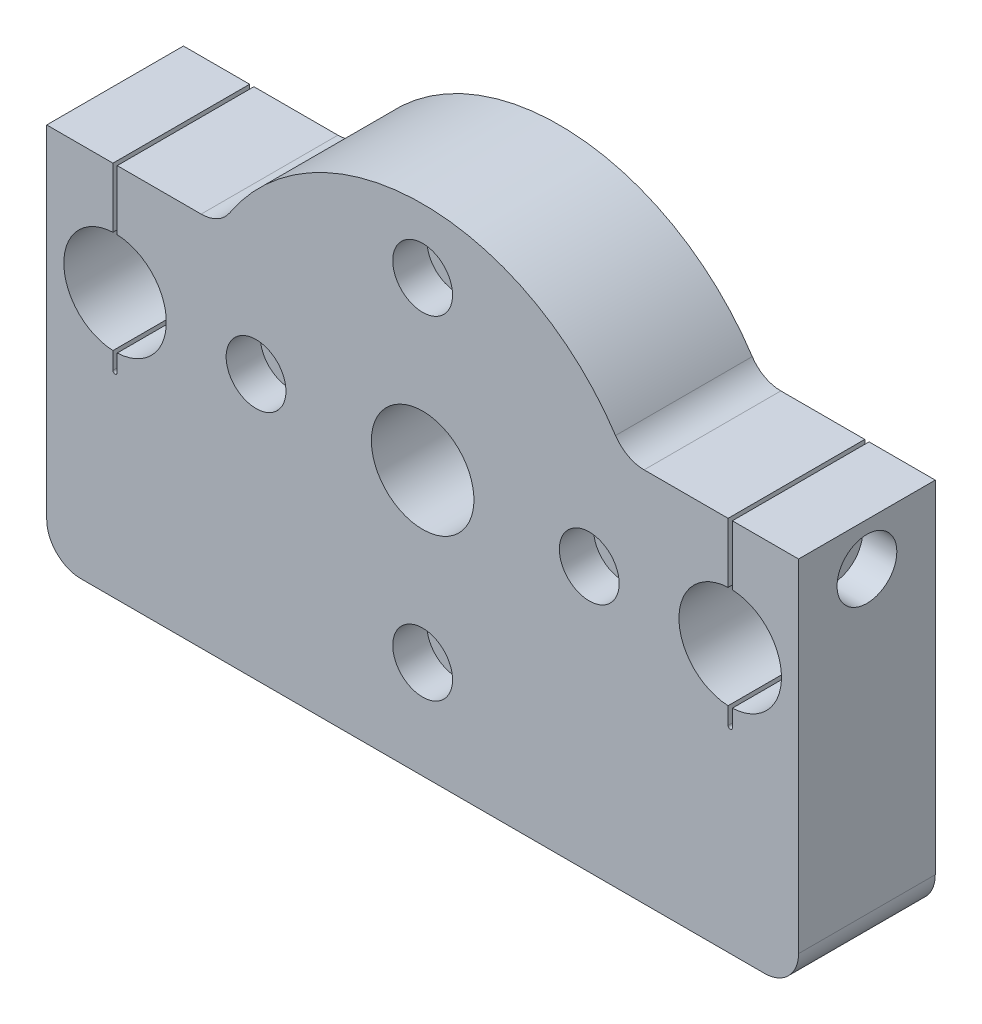
SolidWorks part; units mm, degrees
material "6061 Alloy"
ref_plane "Front" through (0, 0, 0) normal (0, 0, 1) x (1, 0, 0)
ref_plane "Top" through (0, 0, 0) normal (0, 1, 0) x (1, 0, 0)
ref_plane "Right" through (0, 0, 0) normal (1, 0, 0) x (0, 0, -1)
ref_axis "Axis" through (0, 0, -80.9) along (0, 0, 1)
sketch "Bolt circle" plane through (0, 0, 0) normal (0, 0, 1) x (1, 0, 0)
  line L0 (0, 36.5125) -> (0, 25.4) construction
  line L3 (37.5671, 20.6375) -> (69.85, 20.6375)
  line L5 (37.5671, 20.6375) -> (-37.5671, 20.6375) construction
  line L6 (-37.5671, 20.6375) -> (-69.85, 20.6375)
  line L30 (69.85, 20.6375) -> (69.85, -49.2125)
  line L31 (69.85, -49.2125) -> (-69.85, -49.2125)
  line L34 (-69.85, 20.6375) -> (-69.85, -49.2125)
  line L35 (0, 0) -> (0, -49.2125) construction
  circle A0 centre (0, 0) radius 36.5125 construction
  circle A1 centre (0, 0) radius 25.4 construction
  circle A2 centre (0, 0) radius 30.9562 construction
  arc A5 (-37.5671, 20.6375) -> (37.5671, 20.6375) centre (0, 0) cw
  circle A7 centre (0, 0) radius 12.7 construction
  point P0 (0, -36.5125)
  point P7 (0, 30.9562)
  point P34 (0, 42.8625)
  dimension "D1" = 73.025
  dimension "D2" = 50.8
  dimension "D3" = 69.85
  dimension "D12" = 139.7
  dimension "D13" = 25.4
  dimension "D4" = 12.7
  dimension "D16" = 6.35
extrude "Base" add sketch "Bolt circle" along normal mid plane 25.4
hole_wizard "Tube counterbore" positions "Sketch7" profile "Sketch6" counterbore size "1/4" standard "Ansi Inch" end condition through all
sketch "Sketch7" plane through (0, 0, 12.7) normal (0, 0, 1) x (1, 0, 0)
  circle A0 centre (0, 0) radius 30.9562 construction
  point P1 (0, 30.9562)
  dimension "D1" = 61.9125
sketch "Sketch6" plane through (0, 30.9562, 12.7) normal (1, 0, 0) x (0, -1, 0)
  line L0 (0, 0) -> (0, 25.4)
  line L1 (0, 25.4) -> (3.3782, 25.4)
  line L3 (3.3782, 25.4) -> (3.3782, 6.35)
  line L4 (3.3782, 6.35) -> (5.5562, 6.35)
  line L5 (5.5562, 6.35) -> (5.5562, 0)
  line L7 (5.5562, 0) -> (0, 0)
  line L11 (0, -6.35) -> (0, 107.95) construction
  dimension "Thru Hole Dia." = 6.7564
  dimension "Thru Hole Depth" = 25.4
  dimension "C'Bore Dia." = 11.1125
  dimension "C'Bore Depth" = 6.35
cosmetic thread "Hole Thread2" parameters "D2"=16.7564
pattern_circular "Tube counterbore pattern" count 4 over 360 about axis through (0, 0, -80.9) along (0, 0, 1) of "Tube counterbore"
sketch "Sketch8" plane through (0, 0, -12.7) normal (0, 0, -1) x (-1, 0, 0)
  circle A0 centre (0, 0) radius 36.5125
  dimension "D1" = 73.025
extrude "Structure_tube_recess" cut sketch "Sketch8" against normal blind 7.62
sketch "Sketch9" plane through (0, 0, -5.08) normal (0, 0, -1) x (-1, 0, 0)
  circle A0 centre (0, 0) radius 9.525
  dimension "D1" = 19.05
extrude "Lead_screw_thru_hole" cut sketch "Sketch9" against normal through all
sketch "Sketch13" plane through (0, 0, 12.7) normal (0, 0, 1) x (1, 0, 0)
  line L0 (0, 0) -> (0, -62.7576) construction
  circle A0 centre (57.15, 0) radius 9.525
  circle A1 centre (-57.15, 0) radius 9.525
  dimension "D3" = 19.05
  dimension "D1" = 114.3
extrude "Rail_bore_pilot_hole" cut sketch "Sketch13" against normal through all
sketch "Sketch14" plane through (0, 0, -5.08) normal (0, 0, -1) x (-1, 0, 0)
  line L0 (20.6813, 24.0896) -> (19.6028, 22.9247)
  line L1 (24.176, 20.854) -> (23.0974, 19.6891)
  line L2 (21.8894, 21.8894) -> (-21.8894, -21.8894) construction
  line L3 (20.1421, 23.5072) -> (23.6367, 20.2716) construction
  line L4 (50, 0) -> (-50, 0) construction
  circle A0 centre (-21.8894, -21.8894) radius 2.3813
  arc A1 (24.176, 20.854) -> (20.6813, 24.0896) centre (22.4286, 22.4718) ccw
  arc A2 (23.0974, 19.6891) -> (19.6028, 22.9247) centre (21.3501, 21.3069) cw
  circle A3 centre (21.8894, 21.8894) radius 2.3813 construction
  circle A4 centre (0, 0) radius 30.9563 construction
  point P11 (20.1421, 23.5072)
  dimension "D2" = 61.9125
  dimension "D3" = 4.7625
  dimension "D1" = 1.5875
  dimension "D4" = 45
extrude "Alignment_features" cut sketch "Sketch14" against normal blind 6.35
fillet "Generic_rounding_fillet" radius 6.35 4 edges at (-69.85, -49.2125, 0) (69.85, -49.2125, 0) (37.5671, 20.6375, 0) (-37.5671, 20.6375, 0)
sketch "Sketch15" plane through (0, 0, -12.7) normal (0, 0, -1) x (-1, 0, 0)
  line L1 (56.7531, -9.5167) -> (56.7531, -12.7)
  line L2 (56.7531, 20.6375) -> (57.5469, 20.6375)
  line L3 (56.7531, 20.6375) -> (56.7531, 9.5167)
  line L4 (56.7531, 9.5167) -> (57.5469, 9.5167)
  line L5 (57.5469, 20.6375) -> (57.5469, 9.5167)
  line L6 (57.5469, -12.7) -> (57.5469, -9.5167)
  line L7 (57.15, -13.0969) -> (57.15, 20.6375) construction
  line L8 (41.1527, 20.6375) -> (69.85, 20.6375) construction
  line L9 (0, -49.2125) -> (0, 42.8625) construction
  line L10 (63.5, -49.2125) -> (-63.5, -49.2125) construction
  line L11 (-57.15, -13.0969) -> (-57.15, 20.6375) construction
  line L12 (-57.5469, -12.7) -> (-57.5469, -9.5167)
  line L13 (-57.5469, 20.6375) -> (-57.5469, 9.5167)
  line L14 (-56.7531, 9.5167) -> (-57.5469, 9.5167)
  line L15 (-56.7531, 20.6375) -> (-56.7531, 9.5167)
  line L16 (-56.7531, 20.6375) -> (-57.5469, 20.6375)
  line L17 (-56.7531, -9.5167) -> (-56.7531, -12.7)
  circle A0 centre (57.15, 0) radius 9.525 construction
  arc A1 (56.7531, -9.5167) -> (57.5469, -9.5167) centre (57.15, 0) ccw
  arc A2 (56.7531, -12.7) -> (57.5469, -12.7) centre (57.15, -12.7) ccw
  arc A3 (35.8427, 23.5052) -> (-35.8427, 23.5052) centre (0, 0) ccw construction
  arc A4 (-56.7531, -12.7) -> (-57.5469, -12.7) centre (-57.15, -12.7) cw
  arc A5 (-56.7531, -9.5167) -> (-57.5469, -9.5167) centre (-57.15, 0) cw
  dimension "D1" = 0.7937
  dimension "D2" = 12.7
extrude "Flexure_slits" cut sketch "Sketch15" against normal through all
hole_wizard "Flexure_clamp_counterbore" positions "Sketch17" profile "Sketch16" counterbore size "1/4" standard "Ansi Inch" end condition up to next
sketch "Sketch17" plane through (-69.85, 5.7723, 0.2581) normal (-1, 0, 0) x (0, 0, 1)
  line L1 (-0.2581, -55.7723) -> (-0.2581, 44.2277) construction
  line L3 (12.4419, 14.8652) -> (-12.9581, 14.8652) construction
  point P0 (-0.2581, 6.9277)
  dimension "D1" = 7.9375
sketch "Sketch16" plane through (-69.85, 12.7, 0) normal (0, 1, 0) x (0, 0, 1)
  line L0 (0, 0) -> (0, 12.3031)
  line L1 (0, 12.3031) -> (3.3782, 12.3031)
  line L3 (3.3782, 12.3031) -> (3.3782, 6.35)
  line L4 (3.3782, 6.35) -> (5.5562, 6.35)
  line L5 (5.5562, 6.35) -> (5.5562, 0)
  line L7 (5.5562, 0) -> (0, 0)
  line L11 (0, -6.35) -> (0, 107.95) construction
  dimension "Thru Hole Dia." = 6.7564
  dimension "Thru Hole Depth" = 12.3031
  dimension "C'Bore Dia." = 11.1125
  dimension "C'Bore Depth" = 6.35
hole_wizard "Flexure_clamp_threads" positions "Sketch19" profile "Sketch18" tap size "1/4-20" standard "Ansi Inch"
sketch "Sketch19" plane through (-56.7531, 0, 0) normal (-1, 0, 0) x (0, 0, 1)
  point P0 (0, 12.7)
sketch "Sketch18" plane through (-56.7531, 12.7, 0) normal (0, 1, 0) x (0, 0, 1)
  line L0 (0, 0) -> (0, 18.0438)
  line L1 (0, 18.0438) -> (2.5527, 16.51)
  line L2 (2.5527, 16.51) -> (2.5527, 0)
  line L5 (2.5527, 0) -> (0, 0)
  line L10 (0, 18.0438) -> (-2.5527, 16.51) construction
  line L11 (0, -6.35) -> (0, 107.95) construction
  dimension "Tap Drill Dia." = 5.1054
  dimension "Tap Drill Depth" = 16.51
  dimension "Drill Angle" = 118
cosmetic thread "Hole Thread3" parameters "D1"=12.7, "D2"=6.35
mirror "Flexure_clamp_fastener_holes" about plane through (0, 0, 0) normal (1, 0, 0) of "Flexure_clamp_threads", "Flexure_clamp_counterbore"
sketch "Sketch20" plane through (0, -49.2125, 0) normal (0, -1, 0) x (1, 0, 0)
  circle A0 centre (0, 0) radius 4.7625
  dimension "D1" = 9.525
extrude "Point_mount_bore" [suppressed] cut sketch "Sketch20" against normal blind 6.35
